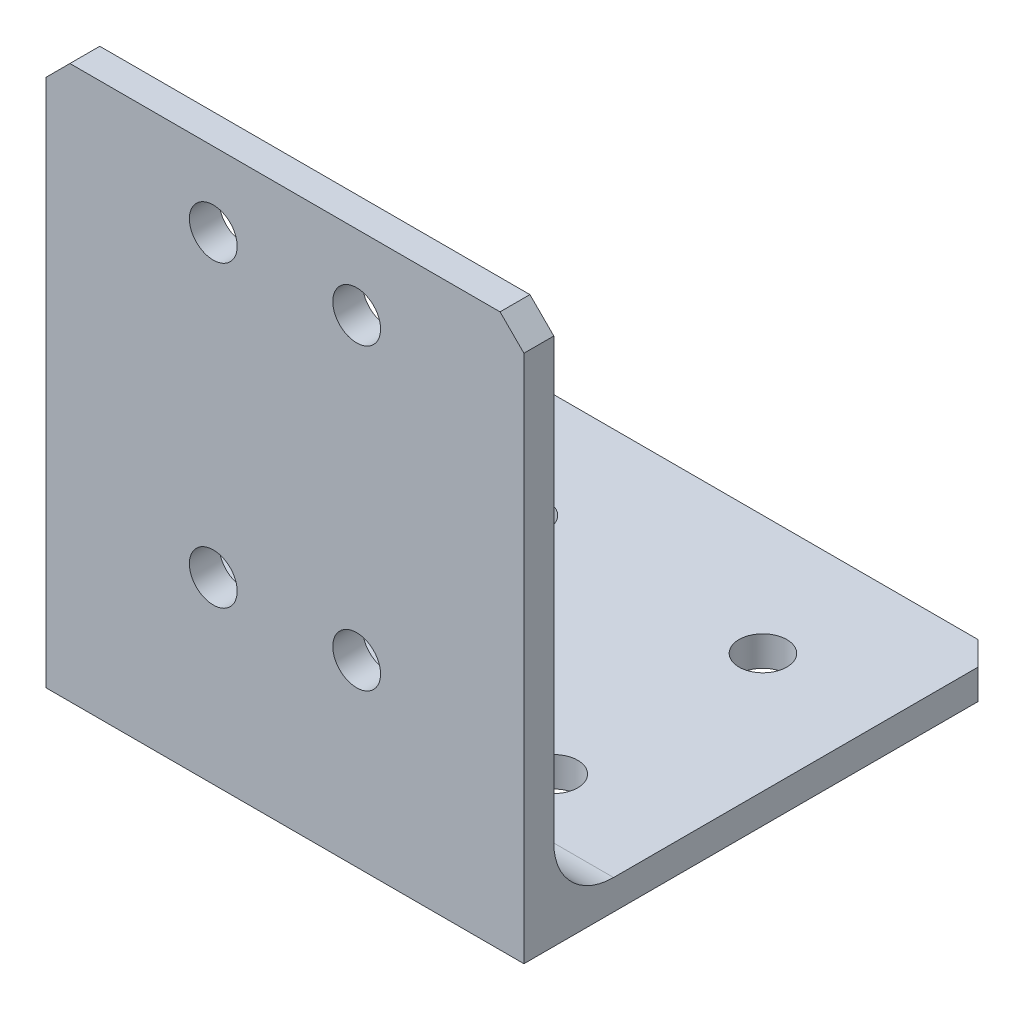
SolidWorks part; units mm, degrees
ref_plane "Front Plane" through (0, 0, 0) normal (0, 0, 1) x (1, 0, 0)
ref_plane "Top Plane" through (0, 0, 0) normal (0, 1, 0) x (1, 0, 0)
ref_plane "Right Plane" through (0, 0, 0) normal (1, 0, 0) x (0, 0, -1)
sketch "Sketch1" plane through (0, 0, 0) normal (1, 0, 0) x (0, 0, -1)
  line L0 (0, 0) -> (0, 58.7375)
  line L1 (0, 58.7375) -> (3.175, 58.7375)
  line L2 (3.175, 58.7375) -> (3.175, 3.175)
  line L3 (3.175, 3.175) -> (50.8, 3.175)
  line L4 (50.8, 3.175) -> (50.8, 0)
  line L5 (50.8, 0) -> (0, 0)
  dimension "D1" = 58.7375
  dimension "D2" = 3.175
  dimension "D3" = 50.8
extrude "Boss-Extrude1" add sketch "Sketch1" along normal blind 50.8
sketch "Sketch2" plane through (0, 0, 0) normal (0, 0, 1) x (1, 0, 0)
  line L2 (50.8, 0) -> (0, 0) construction
  line L4 (25.4, 0) -> (25.4, 58.7375) construction
  line L5 (50.8, 58.7375) -> (0, 58.7375) construction
  circle A0 centre (17.78, 50.8) radius 2.54
  circle A1 centre (17.78, 19.05) radius 2.54
  circle A4 centre (33.02, 19.05) radius 2.54
  circle A5 centre (33.02, 50.8) radius 2.54
  dimension "D1" = 5.08
  dimension "D2" = 7.62
  dimension "D4" = 19.05
  dimension "D5" = 31.75
extrude "Cut-Extrude1" cut sketch "Sketch2" against normal through all
sketch "Sketch3" plane through (0, 0, 0) normal (0, -1, 0) x (1, 0, 0)
  line L0 (50.8, -50.8) -> (0, -50.8) construction
  line L1 (50.8, 0) -> (0, 0) construction
  line L2 (50.8, 0) -> (50.8, -50.8) construction
  line L3 (0, 0) -> (0, -50.8) construction
  circle A0 centre (38.1, -38.1) radius 2.54
  circle A1 centre (38.1, -15.875) radius 2.54
  circle A2 centre (12.7, -38.1) radius 2.54
  circle A3 centre (12.7, -15.875) radius 2.54
  dimension "D1" = 5.08
  dimension "D2" = 12.7
  dimension "D3" = 15.875
  dimension "D4" = 12.7
  dimension "D5" = 12.7
extrude "Cut-Extrude2" cut sketch "Sketch3" against normal through all
fillet "Fillet1" radius 6.35 1 edges at (25.4, 3.175, -3.175)
chamfer "Chamfer1" distance 2.54 angle 45 4 edges at (50.8, 58.7375, -1.5875) (0, 58.7375, -1.5875) (50.8, 1.5875, -50.8) (0, 1.5875, -50.8)
